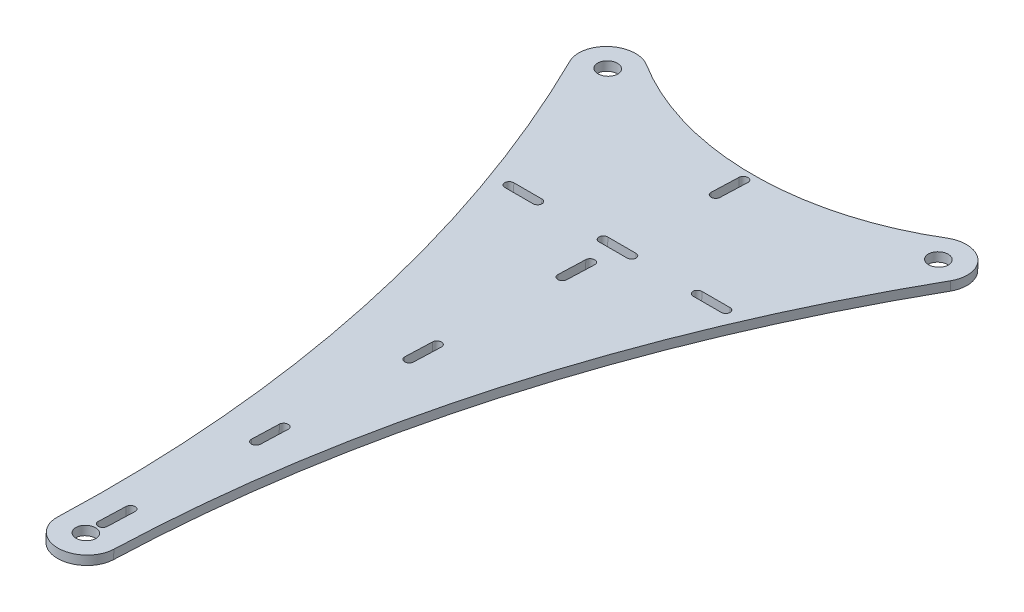
SolidWorks part; units mm, degrees
ref_plane "Front Plane" through (0, 0, 0) normal (0, 0, 1) x (1, 0, 0)
ref_plane "Top Plane" through (0, 0, 0) normal (0, 1, 0) x (1, 0, 0)
ref_plane "Right Plane" through (0, 0, 0) normal (1, 0, 0) x (0, 0, -1)
sketch "Sketch1" plane through (0, 79.1663, -2.7669) normal (0, -0.9994, 0.0349) x (0, -0.0349, -0.9994)
  line L0 (4.8479, 0) -> (-4.8479, 0) construction
  circle A0 centre (-118.8704, 0) radius 3.5
  circle A1 centre (126.4846, -59) radius 3.5
  circle A2 centre (126.4846, 59) radius 3.5
  circle A3 centre (-118.8704, 0) radius 10
  circle A4 centre (126.4846, -59) radius 10
  circle A5 centre (126.4846, 59) radius 10
  arc A6 (134.9245, 53.6364) -> (134.9245, -53.6364) centre (219.3232, 0) ccw
  arc A7 (121.9382, -67.9067) -> (-118.8704, -10) centre (-118.8704, -539.6619) ccw
  arc A8 (121.9382, 67.9067) -> (-118.8704, 10) centre (-118.8704, 539.6619) cw
  ellipse E0 centre (-118.8704, 0) end of major axis (-118.8704, 3.225) minor radius 3.223 construction
  ellipse E3 centre (126.9846, -59) end of major axis (126.9846, -56.075) minor radius 2.9032 construction
  point P16 (126.9846, -59)
  point P25 (0, 0)
  dimension "D1" = 7
  dimension "D3" = 7
  dimension "D4" = 20
  dimension "D5" = 100
  dimension "D2" = 0.5
extrude "Boss-Extrude1" add sketch "Sketch1" along normal blind 3.175 contours A5 A8 A3 A7 A4 A6 | A3 A0 | A5 A2 | A4 A1 region at (-6.8711, 83.0783, 109.1641) region at (0, 77.6526, -46.0785) region at (67.2871, 74.5711, -134.2454) region at (-52.4599, 74.9994, -121.9919)
sketch "Sketch2" plane through (0, 75.9932, -2.656) normal (0, -0.9994, 0.0349) x (1, 0, 0)
  line L0 (0, 112.8704) -> (0, 102.8704) construction
  line L1 (1.5875, 112.8704) -> (-1.5875, 112.8704) construction
  line L2 (1.5875, 102.8704) -> (-1.5875, 102.8704) construction
  line L3 (1.5875, 112.8704) -> (1.5875, 102.8704)
  line L4 (-1.5875, 112.8704) -> (-1.5875, 102.8704)
  line L5 (0, -105.9382) -> (0, -115.9382) construction
  line L6 (1.5875, -105.9382) -> (-1.5875, -105.9382) construction
  line L7 (1.5875, -115.9382) -> (-1.5875, -115.9382) construction
  line L8 (1.5875, -105.9382) -> (1.5875, -115.9382)
  line L9 (-1.5875, -105.9382) -> (-1.5875, -115.9382)
  line L10 (0, 58.1683) -> (0, 48.1683) construction
  line L11 (1.5875, 58.1683) -> (1.5875, 48.1683)
  line L12 (-1.5875, 58.1683) -> (-1.5875, 48.1683)
  line L13 (0, 3.4661) -> (0, -6.5339) construction
  line L14 (1.5875, 3.4661) -> (1.5875, -6.5339)
  line L15 (-1.5875, 3.4661) -> (-1.5875, -6.5339)
  line L16 (0, -51.236) -> (0, -61.236) construction
  line L17 (1.5875, -51.236) -> (1.5875, -61.236)
  line L18 (-1.5875, -51.236) -> (-1.5875, -61.236)
  line L19 (1.5875, -6.5339) -> (-1.5875, -6.5339) construction
  line L20 (38.5715, -70.9382) -> (28.5715, -70.9382) construction
  line L21 (38.5715, -72.5257) -> (38.5715, -69.3507) construction
  line L22 (28.5715, -72.5257) -> (28.5715, -69.3507) construction
  line L23 (38.5715, -72.5257) -> (28.5715, -72.5257)
  line L24 (38.5715, -69.3507) -> (28.5715, -69.3507)
  line L25 (5, -70.9382) -> (-5, -70.9382) construction
  line L26 (5, -72.5257) -> (5, -69.3507) construction
  line L27 (-5, -72.5257) -> (-5, -69.3507) construction
  line L28 (5, -72.5257) -> (-5, -72.5257)
  line L29 (5, -69.3507) -> (-5, -69.3507)
  line L30 (-28.5715, -70.9382) -> (-38.5715, -70.9382) construction
  line L31 (-28.5715, -72.5257) -> (-28.5715, -69.3507) construction
  line L32 (-38.5715, -72.5257) -> (-38.5715, -69.3507) construction
  line L33 (-28.5715, -72.5257) -> (-38.5715, -72.5257)
  line L34 (-28.5715, -69.3507) -> (-38.5715, -69.3507)
  arc A0 (1.5875, 112.8704) -> (-1.5875, 112.8704) centre (0, 112.8704) ccw
  arc A1 (-1.5875, 102.8704) -> (1.5875, 102.8704) centre (0, 102.8704) ccw
  arc A2 (1.5875, -105.9382) -> (-1.5875, -105.9382) centre (0, -105.9382) ccw
  arc A3 (-1.5875, -115.9382) -> (1.5875, -115.9382) centre (0, -115.9382) ccw
  arc A4 (1.5875, 58.1683) -> (-1.5875, 58.1683) centre (0, 58.1683) ccw
  arc A5 (-1.5875, 48.1683) -> (1.5875, 48.1683) centre (0, 48.1683) ccw
  arc A6 (1.5875, 3.4661) -> (-1.5875, 3.4661) centre (0, 3.4661) ccw
  arc A7 (-1.5875, -6.5339) -> (1.5875, -6.5339) centre (0, -6.5339) ccw
  arc A8 (1.5875, -51.236) -> (-1.5875, -51.236) centre (0, -51.236) ccw
  arc A9 (-1.5875, -61.236) -> (1.5875, -61.236) centre (0, -61.236) ccw
  arc A10 (38.5715, -72.5257) -> (38.5715, -69.3507) centre (38.5715, -70.9382) ccw
  arc A11 (28.5715, -69.3507) -> (28.5715, -72.5257) centre (28.5715, -70.9382) ccw
  arc A12 (5, -72.5257) -> (5, -69.3507) centre (5, -70.9382) ccw
  arc A13 (-5, -69.3507) -> (-5, -72.5257) centre (-5, -70.9382) ccw
  arc A14 (-28.5715, -72.5257) -> (-28.5715, -69.3507) centre (-28.5715, -70.9382) ccw
  arc A15 (-38.5715, -69.3507) -> (-38.5715, -72.5257) centre (-38.5715, -70.9382) ccw
  point P6 (0, 107.8704)
  point P11 (0, -110.9382)
  point P22 (33.5715, -70.9382)
  point P28 (0, 53.1683)
  point P35 (0, -1.5339)
  point P42 (0, -56.236)
  point P59 (0, -70.9382)
  point P70 (-33.5715, -70.9382)
  dimension "D1" = 4
extrude "Cut-Extrude1" cut sketch "Sketch2" against normal blind 3.175
